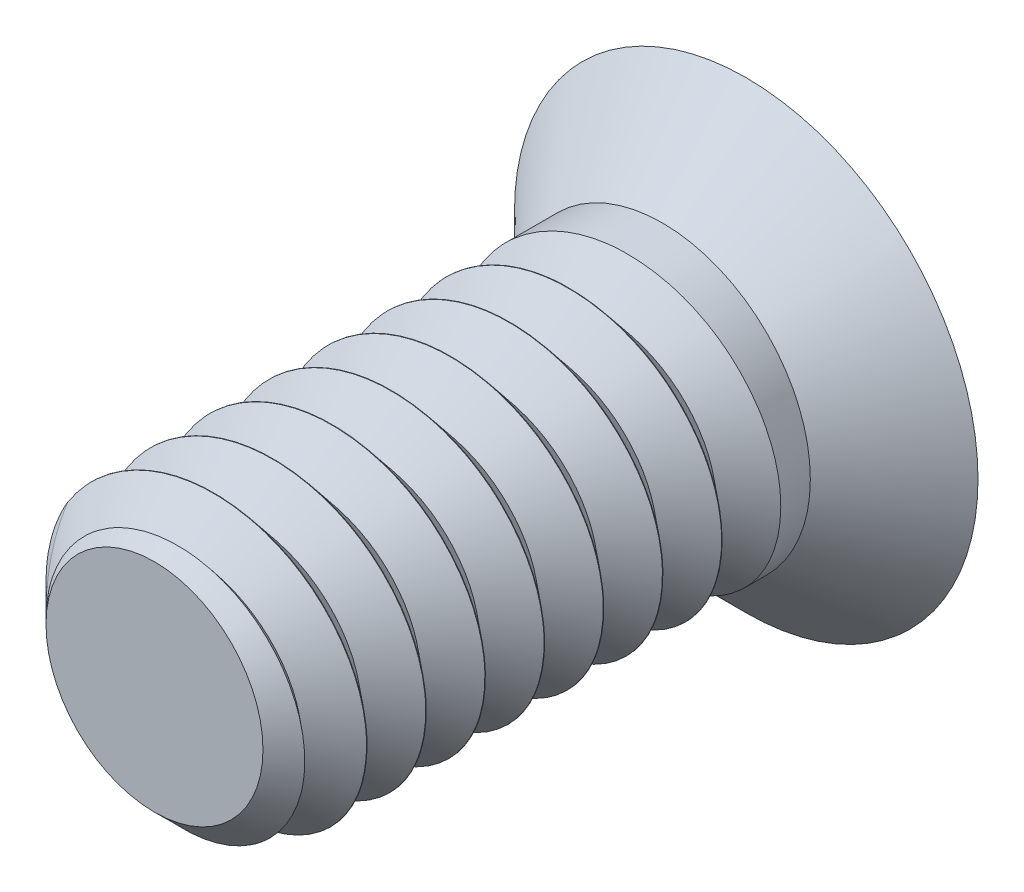
SolidWorks part; units mm, degrees
ref_plane "Front Plane" through (0, 0, 0) normal (0, 0, 1) x (1, 0, 0)
ref_plane "Top Plane" through (0, 0, 0) normal (0, 1, 0) x (1, 0, 0)
ref_plane "Right Plane" through (0, 0, 0) normal (1, 0, 0) x (0, 0, -1)
sketch "Sketch1" plane through (0, 0, 0) normal (0, 0, 1) x (1, 0, 0)
  circle A0 centre (0, 0) radius 3
  dimension "D1" = 6
extrude "Boss-Extrude1" add sketch "Sketch1" along normal blind 10
ref_plane "Plane4" through (0, 0, 0.6) normal (0, 0, 1) x (1, 0, 0)
chamfer "Chamfer3" distance 0.8 angle 45 1 edges at (3, 0, 10)
sketch "Sketch2" plane through (0, 0, 0.6) normal (0, 0, -1) x (-1, 0, 0)
  circle A0 centre (0, 0) radius 3
  circle A2 centre (0, 0) radius 3 construction
curve "Helix/Spiral1" pitch 1.2 height 35 turns 29.1667
sketch "Sketch3" plane through (0, 0, 0) normal (1, 0, 0) x (0, 0, -1)
  line L0 (-1.195, -3) -> (-0.005, -3)
  line L1 (-0.005, -3) -> (-0.6, -2.28)
  line L2 (-0.6, -2.28) -> (-1.195, -3)
  line L3 (-0.01, -3) -> (-9.2, -3) construction
  line L4 (-0.6, 5.17) -> (-0.6, -5.17) construction
  point P3 (-0.6, -3)
  dimension "D2" = 0.72
  dimension "D1" = 1.19
sweep "Cut-Sweep3" cut profiles "Sketch3" path "Helix/Spiral1" align with end faces yes
sketch "Sketch5" plane through (0, 0, 0) normal (0, 0, -1) x (-1, 0, 0)
  circle A0 centre (0, 0) radius 4.9
  dimension "D1" = 9.8
extrude "Boss-Extrude2" add sketch "Sketch5" along normal blind 2
sketch "Sketch4" plane through (0, 0, -2) normal (0, 0, -1) x (-1, 0, 0)
  line L0 (0.5, 2) -> (-0.5, 2)
  line L7 (-0.5, 2) -> (-0.5, 0.5)
  line L8 (-0.5, 0.5) -> (-2, 0.5)
  line L9 (-2, 0.5) -> (-2, -0.5)
  line L10 (-2, -0.5) -> (-0.5, -0.5)
  line L11 (-0.5, -0.5) -> (-0.5, -2)
  line L12 (-0.5, -2) -> (0.5, -2)
  line L13 (0.5, -2) -> (0.5, -0.5)
  line L14 (0.5, -0.5) -> (2, -0.5)
  line L15 (2, -0.5) -> (2, 0.5)
  line L16 (2, 0.5) -> (0.5, 0.5)
  line L17 (0.5, 0.5) -> (0.5, 2)
  line L18 (-0.5, 0.5) -> (-0.5, -0.5) construction
  line L19 (-0.5, -0.5) -> (0.5, -0.5) construction
  point P6 (0, 0)
  point P9 (-0.5, 0)
  point P14 (0, -0.5)
  dimension "D1" = 4
  dimension "D2" = 1
extrude "Cut-Extrude1" cut sketch "Sketch4" against normal blind 3
chamfer "Chamfer2" distance 2.2 angle 45 1 edges at (-4.9, 0, 0)
equation "\"cleatShaftLen\" = 3"
equation "\"cleatHeadLen\" = 4mm"
equation "\"cleatHeadGirth\" = 12mm"
equation "\"cleatShaftGirth\" = 8mm"
equation "\"cleatTolOffset\" = 0.4mm"
equation "\"cleatCham\" = 1mm"
equation "\"cleatSpacing\" = 30mm"
equation "\"cleatTriangleAngle\" = 25deg"
equation "\"cleatMinimumTriangleAngle\" = 12deg"
equation "\"nCleats\" = 2"
equation "\"threadID\" = 8.3mm"
equation "\"threadPitch\" = 2mm"
equation "\"threadOD\" = 10.7mm"
equation "\"cleatFemShaftLen\" = \"cleatShaftLen\" - \"cleatTolOffset\""
equation "\"cleatFemHeadLen\" = \"cleatHeadLen\" + \"cleatTolOffset\" * 1.25"
equation "\"cleatFemHeadGirth\" = \"cleatHeadGirth\" + \"cleatTolOffset\""
equation "\"cleatFemShaftGirth\" = \"cleatShaftGirth\" + \"cleatTolOffset\""
equation "\"lip\" = 2mm"
equation "\"cubeCham\" = 0.7mm"
equation "\"cubeCutoutPadding\" = 3mm"
equation "\"wall\" = 3mm"
equation "\"cleatLen\" = \"cleatShaftLen\" + \"cleatHeadLen\""
equation "\"coverThickness\" = 2mm"
equation "\"plugDepth\" = 4mm"
equation "\"bottomChamOffset\" = 1.8mm"
equation "\"maleHelperAngle\" = 45deg"
equation "\"maleHelperAngle2\" = 35deg"
equation "\"stFactor\" = 0.6"
equation "\"stID\" = \"threadID\" * \"stFactor\""
equation "\"stOD\" = \"threadOD\" * \"stFactor\""
equation "\"stPitch\" = \"threadPitch\" * \"stFactor\""
equation "\"temp\" = 0"
equation "\"threadMaleOD\" = 10.0mm"
equation "\"stMaleOD\" = \"threadMaleOD\" * \"stFactor\""
equation "\"D1@Sketch1\"=\"stMaleOD\""
equation "\"D1@Boss-Extrude1\"=10mm"
equation "\"D2@Sketch3\"=(\"stOD\"-\"stID\")/2"
equation "\"D1@Sketch3\"=\"stPitch\"-0.01"
equation "\"D1@Boss-Extrude2\"= \"stSocketHeadLen\""
equation "\"stProtrusion\" = (\"stOD\" - \"stID\") / 2"
equation "\"stHexDiam\" = 2.5mm"
equation "\"stHexPad\" = 0.08mm"
equation "\"stSocketHeadProtrusion\" = 0.65mm"
equation "\"stSocketHeadLen\" = 1.2mm"
equation "\"stSocketHeadLenPad\" = 0.1mm"
equation "\"stSocketHeadCounterboreDepth\" = \"stSocketHeadLen\" + \"stSocketHeadLenPad\""
equation "\"stDriverDepth\" = 2mm"
equation "\"stNutODPad\" = 3mm"
equation "\"stNutDiam\" = \"stOD\" + \"stNutODPad\""
equation "\"stNutHeight\" = 3mm"
equation "\"stNutCham\" = 0.4mm"
equation "\"stSocketHeadDiam\" = \"stOD\" + \"stSocketHeadProtrusion\""
equation "\"threadMaleSocketDiam\" = 15.0mm"
equation "\"threadMaleHex\" = 6mm"
equation "\"wall2\" = 4.15mm"
equation "\"plugCornerFill\" = 3mm"
equation "\"cleatFemLen\" = \"cleatFemShaftLen\" + \"cleatFemHeadLen\""
equation "\"fsg\" = \"cleatFemShaftGirth\""
equation "\"fsl\" = \"cleatFemShaftLen\""
equation "\"fhg\" = \"cleatFemHeadGirth\""
equation "\"fhl\" = \"cleatFemHeadLen\""
equation "\"msg\" = \"cleatShaftGirth\""
equation "\"msl\" = \"cleatShaftLen\""
equation "\"mhg\" = \"cleatHeadGirth\""
equation "\"mhl\" = \"cleatHeadLen\""
equation "\"threadProtrusion\" = (\"threadOD\" - \"threadID\") / 2"
equation "\"stFlatHeadDiamMale\" = 9.4mm"
equation "\"stFlatHeadDiamFemale\" = 9.6mm"
equation "\"stFlatHeadChamAngle\" = 45deg"
equation "\"stFlatHeadAxialLenMale\" = 1.7mm"
equation "\"stFlatHeadAxialLenFem\" = 1.9mm"
equation "\"cubeCutoutFem\" = \"cleatSpacing\" - \"cleatLen\" - 2*\"wall2\""
